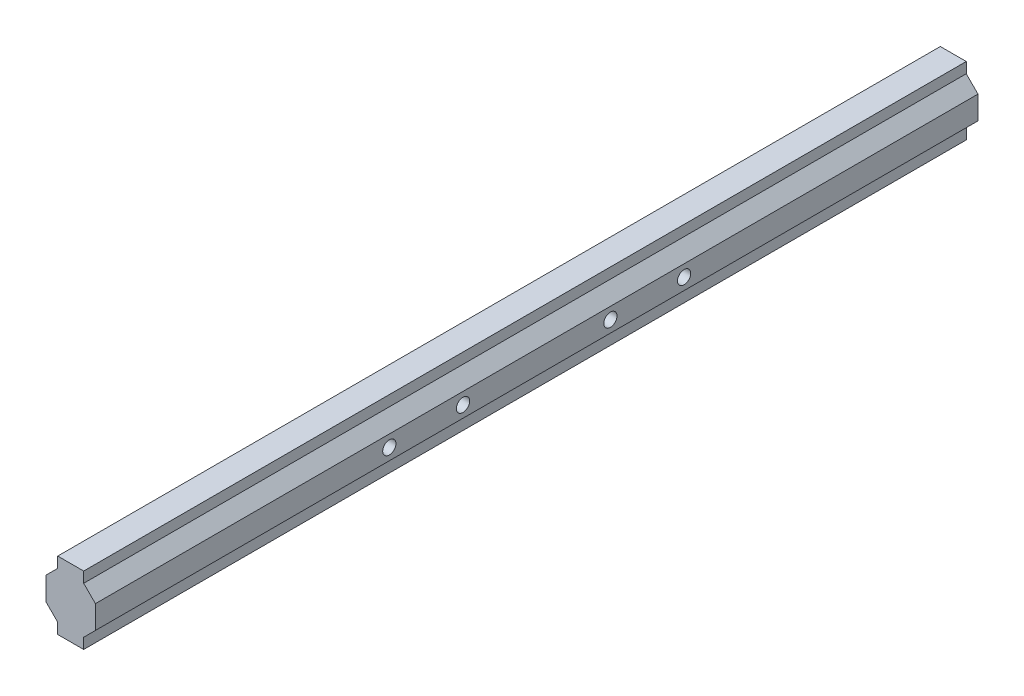
SolidWorks part; units mm, degrees
ref_plane "Front Plane" through (0, 0, 0) normal (0, 0, 1) x (1, 0, 0)
ref_plane "Top Plane" through (0, 0, 0) normal (0, 1, 0) x (1, 0, 0)
ref_plane "Right Plane" through (0, 0, 0) normal (1, 0, 0) x (0, 0, -1)
sketch "Sketch1" plane through (0, 0, 116.1066) normal (0, 0, 1) x (1, 0, 0)
  line L0 (-39.5503, 5.2942) -> (-36.8896, 7.9549)
  line L1 (-36.8896, 7.9549) -> (-36.8896, 10.362)
  line L2 (-36.8896, 10.362) -> (-31.011, 10.362)
  line L3 (-31.011, 7.9549) -> (-28.3503, 5.2942)
  line L4 (-28.3503, 5.2942) -> (-28.3503, 0.0298)
  line L5 (-28.3503, 0.0298) -> (-31.011, -2.6309)
  line L6 (-31.011, -2.6309) -> (-31.011, -5.038)
  line L7 (-31.011, -5.038) -> (-36.8896, -5.038)
  line L8 (-36.8896, -5.038) -> (-36.8896, -2.6309)
  line L9 (-36.8896, -2.6309) -> (-39.5503, 0.0298)
  line L10 (-39.5503, 0.0298) -> (-39.5503, 5.2942)
  line L11 (-31.011, 10.362) -> (-31.011, 7.9549)
  line L12 (-37.3896, 10.862) -> (-30.511, 10.862) construction
  line L13 (-37.3896, -5.538) -> (-30.511, -5.538) construction
  line L14 (-27.8503, 5.4185) -> (-27.8503, -0.0945) construction
  line L15 (-40.0503, 5.4185) -> (-40.0503, -0.0945) construction
  line L16 (-39.9917, 5.5599) -> (-37.3896, 8.162) construction
  line L17 (-37.3896, 8.162) -> (-37.3896, 10.862) construction
  line L18 (-30.511, 8.162) -> (-30.511, 10.862) construction
  line L19 (-27.9089, 5.5599) -> (-30.511, 8.162) construction
  line L20 (-27.9089, -0.2359) -> (-30.511, -2.838) construction
  line L21 (-30.511, -2.838) -> (-30.511, -5.538) construction
  line L22 (-37.3896, -2.838) -> (-37.3896, -5.538) construction
  line L23 (-39.9917, -0.2359) -> (-37.3896, -2.838) construction
  point P24 (-37.3896, 9.512)
  dimension "D1" = 0.5
  dimension "D2" = 0.5
  dimension "D3" = 0.5
  dimension "D4" = 0.5
  dimension "D5" = 0.5
  dimension "D6" = 0.5
  dimension "D7" = 0.5
  dimension "D8" = 0.5
  dimension "D9" = 0.5
  dimension "D10" = 0.5
  dimension "D11" = 0.5
  dimension "D12" = 0.5
extrude "Boss-Extrude1" add sketch "Sketch1" along normal blind 200
sketch "Sketch2" plane through (-28.3503, 0, 0) normal (1, 0, 0) x (0, 0, -1)
  line L0 (-216.1066, 5.2942) -> (-216.1066, 0.0298) construction
  line L1 (-316.1066, 5.2942) -> (-116.1066, 5.2942) construction
  line L2 (-316.1066, 0.0298) -> (-116.1066, 0.0298) construction
  line L3 (-316.1066, 0.0298) -> (-316.1066, 5.2942) construction
  circle A0 centre (-249.5066, 2.662) radius 1.5
  circle A1 centre (-232.8066, 2.662) radius 1.5
  circle A2 centre (-199.4066, 2.662) radius 1.5
  circle A3 centre (-182.7066, 2.662) radius 1.5
  point P12 (-316.1066, 2.662)
  dimension "D1" = 3
  dimension "D2" = 3
  dimension "D3" = 0
  dimension "D4" = 0
  dimension "D5" = 16.7
  dimension "D6" = 16.7
extrude "Cut-Extrude1" cut sketch "Sketch2" against normal blind 20
